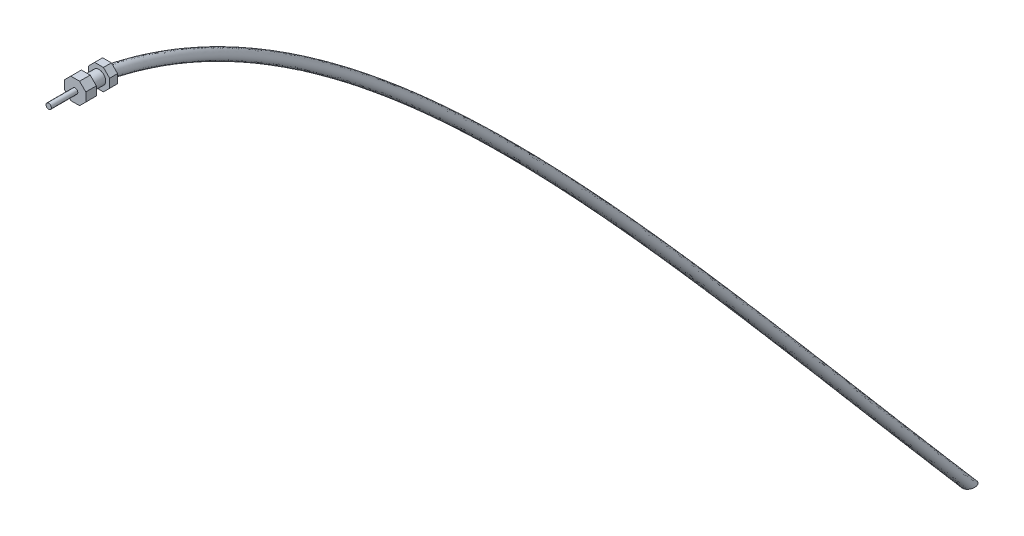
SolidWorks part; units mm, degrees
ref_plane "Front Plane" through (0, 0, 0) normal (0, 0, 1) x (1, 0, 0)
ref_plane "Top Plane" through (0, 0, 0) normal (0, 1, 0) x (1, 0, 0)
ref_plane "Right Plane" through (0, 0, 0) normal (1, 0, 0) x (0, 0, -1)
sketch "Sketch1" plane through (0, 0, 0) normal (0, 0, 1) x (1, 0, 0)
  circle A0 centre (0, 0) radius 2.5
  dimension "D1" = 5
extrude "Boss-Extrude1" add sketch "Sketch1" along normal mid plane 5
sketch "Sketch2" plane through (0, 0, 2.5) normal (0, 0, 1) x (1, 0, 0)
  line L0 (-1.6569, -4) -> (1.6569, -4)
  line L1 (4, -1.6569) -> (4, 1.6569)
  line L2 (4, 1.6569) -> (1.6569, 4)
  line L3 (1.6569, 4) -> (-1.6569, 4)
  line L4 (-1.6569, 4) -> (-4, 1.6569)
  line L5 (-4, 1.6569) -> (-4, -1.6569)
  line L6 (-4, -1.6569) -> (-1.6569, -4)
  line L7 (1.6569, -4) -> (4, -1.6569)
  circle A0 centre (0, 0) radius 4 construction
  dimension "D1" = 8
extrude "Boss-Extrude2" add sketch "Sketch2" along normal blind 4
sketch "Sketch3" plane through (0, 0, -2.5) normal (0, 0, -1) x (-1, 0, 0)
  line L2 (1.6569, -4) -> (4, -1.6569)
  line L3 (4, -1.6569) -> (4, 1.6569)
  line L4 (4, 1.6569) -> (1.6569, 4)
  line L5 (1.6569, 4) -> (-1.6569, 4)
  line L6 (-1.6569, 4) -> (-4, 1.6569)
  line L7 (-4, 1.6569) -> (-4, -1.6569)
  line L8 (-4, -1.6569) -> (-1.6569, -4)
  line L9 (-1.6569, -4) -> (1.6569, -4)
  circle A0 centre (0, 0) radius 4 construction
  point P0 (-3.1081, 3.0141)
  dimension "D1" = 8
extrude "Boss-Extrude3" add sketch "Sketch3" along normal blind 3
sketch "Sketch4" plane through (0, 0, 6.5) normal (0, 0, 1) x (1, 0, 0)
  circle A0 centre (0, 0) radius 1
  dimension "D1" = 2
extrude "Boss-Extrude4" add sketch "Sketch4" along normal blind 10
ref_plane "Plane1" through (0, 0, 0) normal (-1, 0, 0) x (0, 0, 1)
sketch "Sketch5" plane through (0, 0, 0) normal (-1, 0, 0) x (0, 0, 1)
  line L0 (-5.5, -1.6569) -> (-5.5, 1.6569) construction
  spline S0 degree 3 poles (-5.5, 0) (-103.4694, -19.5695) (-266.5487, -229.9696) (-554.1355, -547.5925) (-555.6646, -353.1151) (-697.7794, -232.0268) knots 0 0 0 0 0.449539 0.697189 1 1 1 1
  point P2 (-831.8676, -498.7146)
  point P4 (-507.9071, -456.5631)
  point P6 (-331.4526, -178.0876)
  point P7 (0, 0)
  dimension "D4" = 677.0207
sketch "Sketch6" plane through (0, 0, -5.5) normal (0, 0, -1) x (-1, 0, 0)
  circle A0 centre (0, 0) radius 2
  dimension "D1" = 4
sweep "Sweep1" add profiles "Sketch6" path "Sketch5"
sketch "Sketch7" plane through (0, 0, 0) normal (1, 0, 0) x (0, 0, -1)
  line L0 (800.8955, -195.1965) -> (596.862, -195.1965)
  line L1 (596.862, -195.1965) -> (579.8579, -297.133)
  line L2 (800.8955, -524.7112) -> (139.7661, -524.7112)
  line L3 (800.8955, -524.7112) -> (800.8955, -195.1965)
  line L5 (139.7661, -524.7112) -> (139.7661, -297.133)
  line L6 (579.8579, -297.133) -> (139.7661, -297.133)
extrude "Cut-Extrude1" cut sketch "Sketch7" against normal mid plane 58
